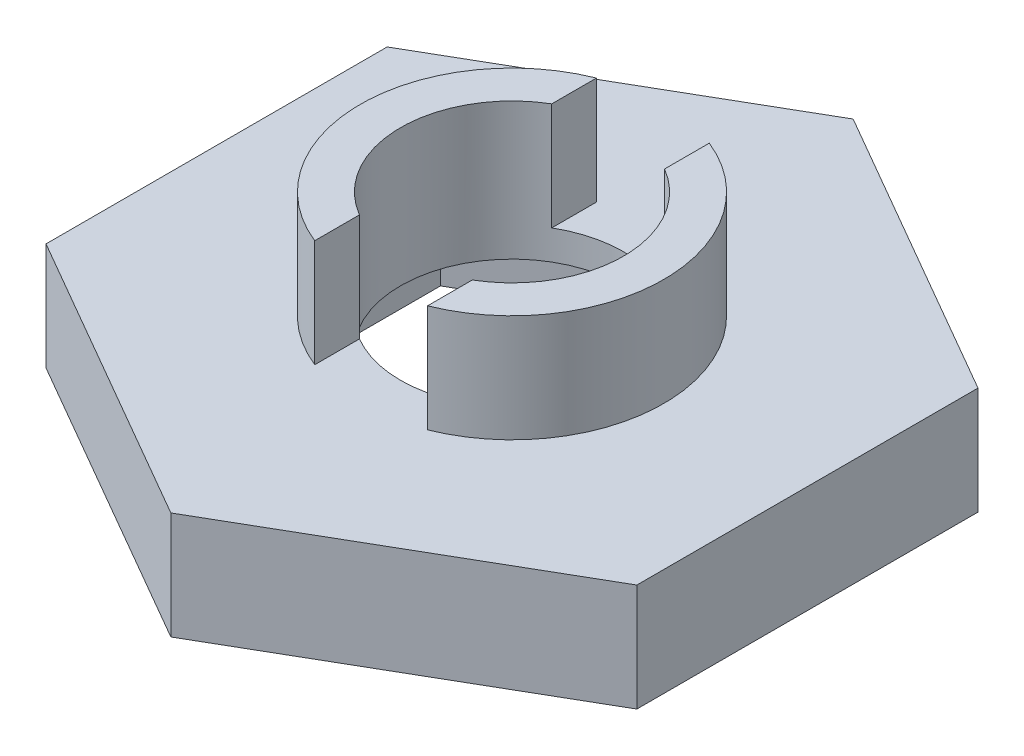
SolidWorks part; units mm, degrees
ref_plane "前视基准面" through (0, 0, 0) normal (0, 0, 1) x (1, 0, 0)
ref_plane "上视基准面" through (0, 0, 0) normal (0, 1, 0) x (1, 0, 0)
ref_plane "右视基准面" through (0, 0, 0) normal (1, 0, 0) x (0, 0, -1)
sketch "草图1" plane through (0, 0, 0) normal (0, 1, 0) x (1, 0, 0)
  circle A0 centre (0, 0) radius 5.65
  circle A1 centre (0, 0) radius 11
  circle A2 centre (0, 0) radius 4.15
  dimension "D1" = 11.3
  dimension "D2" = 22
  dimension "D3" = 1.5
extrude "凸台-拉伸1" add sketch "草图1" along normal blind 8 contours A0 A2 region at (-5.4902, 0, 0)
extrude "凸台-拉伸2" add sketch "草图1<3>" along normal blind 4 contours A1 A0 region at (-10.6889, 0, 0)
sketch "草图1<3>" plane through (0, 0, 0) normal (0, 1, 0) x (1, 0, 0) same geometry as "草图1"
sketch "草图2" plane through (0, 0, 0) normal (0, -1, 0) x (1, 0, 0)
  line L0 (-6, -3.4641) -> (-6, 3.4641) construction
  line L1 (-6, 3.4641) -> (0, 6.9282) construction
  line L2 (0, 6.9282) -> (6, 3.4641) construction
  line L3 (6, 3.4641) -> (6, -3.4641) construction
  line L4 (6, -3.4641) -> (0, -6.9282) construction
  line L5 (0, -6.9282) -> (-6, -3.4641) construction
  line L6 (0, -7.2746) -> (-6.3, -3.6373)
  line L7 (-6.3, -3.6373) -> (-6.3, 3.6373)
  line L8 (-6.3, 3.6373) -> (0, 7.2746)
  line L9 (0, 7.2746) -> (6.3, 3.6373)
  line L10 (6.3, 3.6373) -> (6.3, -3.6373)
  line L11 (6.3, -3.6373) -> (0, -7.2746)
  circle A0 centre (0, 0) radius 6.9282 construction
  dimension "D1" = 12
  dimension "D2" = 0.3
extrude "切除-拉伸1" cut sketch "草图2" against normal blind 2.9
sketch "草图4" plane through (0, 8, 0) normal (0, 1, 0) x (1, 0, 0)
  line L0 (0, 4.1459) -> (0, 5.647) construction
  line L1 (-2.1, 5.2452) -> (-2.1, 3.5795)
  line L2 (2.1, 5.2452) -> (2.1, 3.5795)
  line L3 (2.1, -3.5795) -> (2.1, -5.2452)
  line L4 (-2.1, -3.5795) -> (-2.1, -5.2452)
  circle A0 centre (0, 0) radius 4.15 construction
  circle A1 centre (0, 0) radius 5.65 construction
  circle A2 centre (0, 0) radius 5.65 construction
  arc A3 (-2.1, -3.5795) -> (2.1, -3.5795) centre (0, 0) ccw
  arc A4 (-2.1, -5.2452) -> (2.1, -5.2452) centre (0, 0) ccw
  arc A5 (-2.1, 5.2452) -> (-2.1, -5.2452) centre (0, 0) ccw construction
  arc A6 (-2.1, 3.5795) -> (-2.1, -3.5795) centre (0, 0) ccw construction
  arc A7 (2.1, -5.2452) -> (2.1, 5.2452) centre (0, 0) ccw construction
  arc A8 (2.1, 5.2452) -> (-2.1, 5.2452) centre (0, 0) ccw
  arc A9 (2.1, -3.5795) -> (2.1, 3.5795) centre (0, 0) ccw construction
  arc A10 (2.1, 3.5795) -> (-2.1, 3.5795) centre (0, 0) ccw
  dimension "D1" = 2.1
  dimension "D2" = 2.1
extrude "切除-拉伸3" cut sketch "草图4" against normal up to surface (4 mm away) up to face at (0, 4, 5.65)
sketch "草图6" plane through (0, 0, 0) normal (0, -1, 0) x (1, 0, 0)
  line L0 (6.3, -3.6373) -> (6.3, 3.6373) construction
  line L1 (0, -7.2746) -> (6.3, -3.6373) construction
  line L2 (-6.3, -3.6373) -> (0, -7.2746) construction
  line L3 (-6.3, 3.6373) -> (-6.3, -3.6373) construction
  line L4 (0, 7.2746) -> (-6.3, 3.6373) construction
  line L5 (6.3, 3.6373) -> (0, 7.2746) construction
  line L19 (11, -6.3509) -> (11, 6.3509)
  line L20 (11, 6.3509) -> (0, 12.7017)
  line L21 (0, 12.7017) -> (-11, 6.3509)
  line L22 (-11, 6.3509) -> (-11, -6.3509)
  line L23 (-11, -6.3509) -> (0, -12.7017)
  line L24 (0, -12.7017) -> (11, -6.3509)
  circle A1 centre (0, 0) radius 11
  circle A2 centre (0, 0) radius 11
  circle M14 centre (0, 0) radius 11
  dimension "D1" = 0
extrude "凸台-拉伸4" add sketch "草图6" against normal up to surface (4 mm away) contours L24 L19 M14 | L23 L24 M14 | L22 L23 M14 | L21 L22 M14 | L20 L21 M14 | L19 L20 M14 region at (9.846, 0, -5.6846) region at (9.846, 0, 5.6846) region at (0, 0, -11.3692) region at (0, 0, 11.3692) region at (-9.846, 0, -5.6846) region at (-9.846, 0, 5.6846) up to face at (0, 4, 0)
